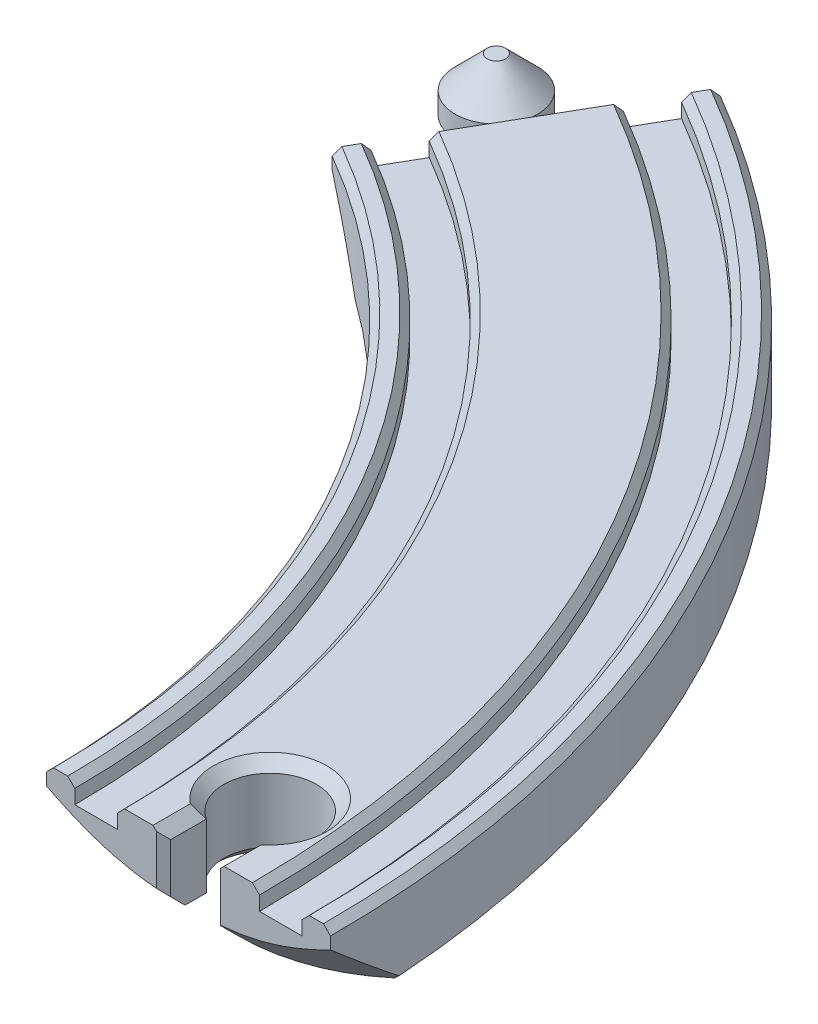
SolidWorks part; units mm, degrees
ref_plane "Front Plane" through (0, 0, 0) normal (0, 0, 1) x (1, 0, 0)
ref_plane "Top Plane" through (0, 0, 0) normal (0, 1, 0) x (1, 0, 0)
ref_plane "Right Plane" through (0, 0, 0) normal (1, 0, 0) x (0, 0, -1)
sketch "Sketch2" plane through (0, 0, 0) normal (0, 0, 1) x (1, 0, 0)
  line L0 (-20, 0) -> (20, 0)
  line L1 (20, 0) -> (20, 12)
  line L2 (20, 12) -> (16, 12)
  line L3 (16, 12) -> (16, 9)
  line L4 (16, 9) -> (10, 9)
  line L5 (10, 9) -> (10, 12)
  line L6 (10, 12) -> (-10, 12)
  line L7 (-10, 12) -> (-10, 9)
  line L8 (-10, 9) -> (-16, 9)
  line L9 (-16, 9) -> (-16, 12)
  line L10 (-16, 12) -> (-20, 12)
  line L11 (-20, 12) -> (-20, 0)
  line L12 (-129.9038, 0) -> (-129.9038, 12)
  point P4 (0, 0)
  dimension "D1" = 40
  dimension "D2" = 12
  dimension "D3" = 3
  dimension "D4" = 4
  dimension "D5" = 6
  dimension "D6" = 129.9038
revolve "Revolve1" add sketch "Sketch2" angle 60 about L12 region at (0, 5.6351, 0)
sketch "Sketch3" plane through (0, 12, 0) normal (0, 1, 0) x (1, 0, 0)
  line L0 (10, 0) -> (-10, 0) construction
  line L2 (-3.5, 0) -> (3.5, 0)
  line L3 (-3.5, 0) -> (-3.5, 11.5)
  line L4 (-3.5, 11.5) -> (3.5, 11.5)
  line L5 (3.5, 0) -> (3.5, 11.5)
  line L6 (-3.5, 0) -> (3.5, 11.5) construction
  line L7 (-3.5, 11.5) -> (3.5, 0) construction
  circle A0 centre (0, 11.5) radius 6.5
  point P4 (0, 5.75)
  point P10 (0, 0)
  line M6 (-10, 0) -> (10, 0)
  dimension "D1" = 13
  dimension "D2" = 11.5
  dimension "D3" = 7
extrude "Cut-Extrude1" cut sketch "Sketch3" against normal through all contours L5 A0 L3 L4 | L3 A0 L5 L4 | A0 L3 L5 M6 region at (0, 12, -2.6732) region at (0, 12, -12.9919) region at (0, 12, -8.4074)
sketch "Sketch4" plane through (0, 12, 0) normal (0, 1, 0) x (1, 0, 0)
  line L0 (-63.7019, 114.6651) -> (-66.2019, 110.3349)
  line L1 (-63.7019, 114.6651) -> (-73.6612, 120.4151)
  line L2 (-66.2019, 110.3349) -> (-76.1612, 116.0849)
  line L3 (-73.6612, 120.4151) -> (-76.1612, 116.0849)
  line L4 (-59.9519, 121.1603) -> (-69.9519, 103.8397) construction
  circle A0 centre (-74.9112, 118.25) radius 5.8
  point P9 (-64.9519, 112.5)
  line M6 (-59.9519, 121.1603) -> (-69.9519, 103.8397)
  dimension "D1" = 11.6
  dimension "D2" = 5
  dimension "D3" = 11.5
extrude "Boss-Extrude1" add sketch "Sketch4" against normal up to surface (12 mm away) contours L1 A0 L2 L3 | L2 A0 L1 L3 region at (-72.4777, 12, -116.845) region at (-75.7915, 12, -118.7583) up to face at (-12.4699, 0, -33.3033)
extrude "Boss-Extrude2" add sketch "Sketch4<3>" against normal blind 7.5 contours A0 L2 L1 M6 region at (-67.5022, 12, -113.9724)
sketch "Sketch4<3>" plane through (0, 12, 0) normal (0, 1, 0) x (1, 0, 0) same geometry as "Sketch4"
extrude "Cut-Extrude2" cut sketch "Sketch4<5>" against normal blind 4.5 contours A0 L2 L1 M6 region at (-67.5022, 12, -113.9724)
sketch "Sketch4<5>" plane through (0, 12, 0) normal (0, 1, 0) x (1, 0, 0) same geometry as "Sketch4"
chamfer "Chamfer2" distance 4.5 angle 45 1 edges at (-80.7112, 12, -118.25)
chamfer "Chamfer5" distance 3 distance2 4.5 1 edges at (-74.9112, 0, -124.05) first distance on face at (-74.9112, 0, -124.05)
chamfer "Chamfer3" distance 1.5 angle 45 6 edges at (0, 0, -18) (0, 12, -18) (3.5, 0, -3.0114) (-3.5, 0, -3.0114) (3.5, 12, -3.0114) (-3.5, 12, -3.0114)
sketch "Sketch17" plane through (31.226, 0, -54.0849) normal (-0.5, 0, 0.866) x (0.866, 0, 0.5)
  line L0 (-118.7665, 10.7665) -> (-118.7665, 0)
  line L1 (-118.7665, 0) -> (-108, 0)
  line L2 (-108, 0) -> (-118.7665, 10.7665)
  line L4 (-83, -1.2652) -> (-83, 10.7665) construction
  dimension "D1" = 25
revolve "Cut-Revolve1" cut sketch "Sketch17" angle 90 about L4
ref_plane "Plane1" through (32.476, 0, -56.25) normal (-0.5, 0, 0.866) x (0.866, 0, 0.5)
mirror "Mirror1" about plane through (32.476, 0, -56.25) normal (-0.5, 0, 0.866) of "Cut-Revolve1"
chamfer "Chamfer4" distance 4.5 angle 45 1 edges at (-64.9519, 0, -112.5)
ref_plane "Plane2" through (-32.476, 0, -56.25) normal (-0.5, 0, -0.866) x (-0.866, 0, 0.5)
mirror "Mirror4" about plane through (-32.476, 0, -56.25) normal (-0.5, 0, -0.866) of "Cut-Revolve1", "Mirror1"
chamfer "Chamfer1" distance 1 angle 45 10 edges at (-0.0833, 12, -74.9519) (-3.5474, 12, -72.9519) (-8.7436, 12, -69.9519) (-26.0641, 12, -59.9519) (-31.2602, 12, -56.9519) (-34.7243, 12, -54.9519) (-0.0833, 0, -74.9519) (-34.7243, 0, -54.9519) (3.5, 7.5085, 0) (-3.5, 7.5085, 0)
